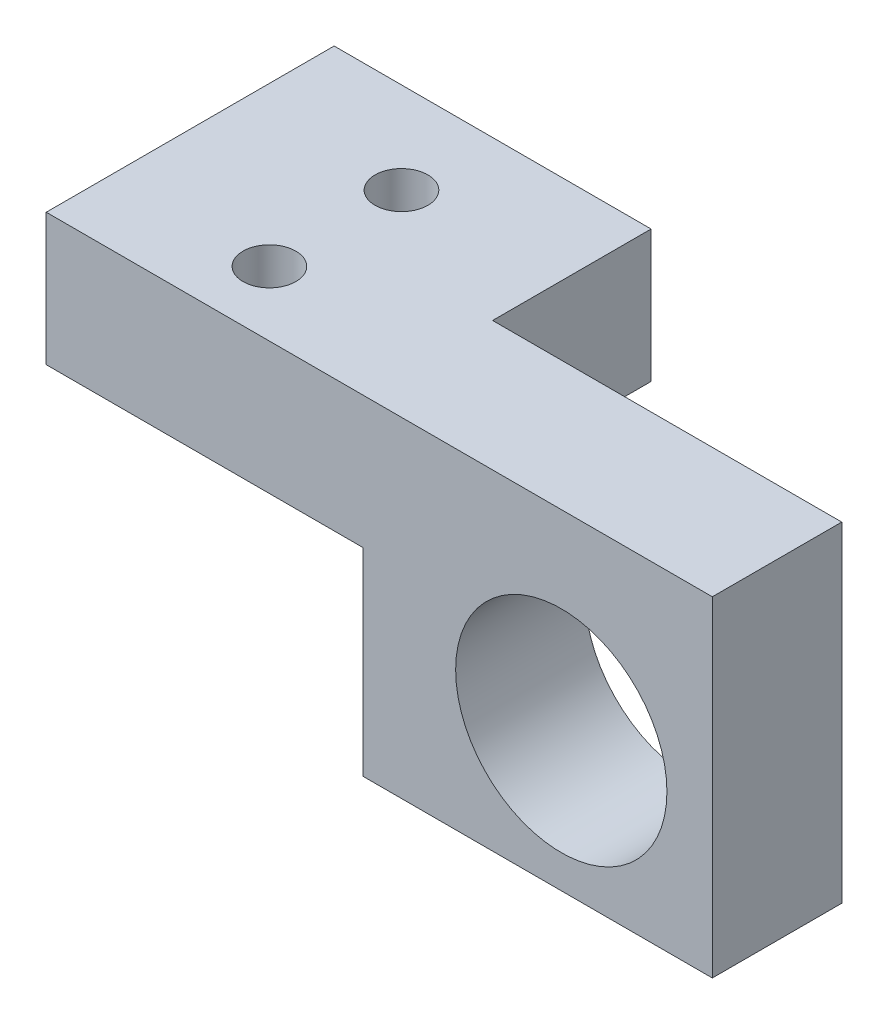
SolidWorks part; units mm, degrees
material "ABS"
ref_plane "Front Plane" through (0, 0, 0) normal (0, 0, 1) x (1, 0, 0)
ref_plane "Top Plane" through (0, 0, 0) normal (0, 1, 0) x (1, 0, 0)
ref_plane "Right Plane" through (0, 0, 0) normal (1, 0, 0) x (0, 0, -1)
sketch "Sketch1" plane through (0, 0, 0) normal (0, 0, 1) x (1, 0, 0)
  line L0 (-24, 15) -> (0, 15)
  line L1 (0, 15) -> (0, 0)
  line L2 (0, 0) -> (93, 0)
  line L3 (93, 0) -> (93, 102.7)
  line L4 (93, 102.7) -> (0, 102.7)
  line L5 (0, 102.7) -> (0, 30)
  line L6 (0, 30) -> (-24, 30)
  line L7 (-24, 30) -> (-24, 15)
  circle A0 centre (15, 10.5) radius 8
  circle A1 centre (70, 72) radius 11
  circle A2 centre (15, 10.5) radius 11
  dimension "D1" = 15
  dimension "D10" = 16
  dimension "D11" = 22
  dimension "D12" = 22
  dimension "D2" = 24
  dimension "D3" = 72.7
  dimension "D4" = 15
  dimension "D5" = 15
  dimension "D6" = 10.5
  dimension "D7" = 82.5061
  dimension "D8" = 72
  dimension "D9" = 93
extrude "Boss-Extrude1" add sketch "Sketch1" along normal blind 4.8 contours A2 L2 L3 L4 L5 L6 L7 L0 L1 A1 | L2 A2 A0 region at (44.5238, 51.0418, 0) region at (8.6656, 19.1141, 0)
sketch "Sketch2" plane through (0, 0, 4.8) normal (0, 0, 1) x (1, 0, 0)
  line L0 (93, 0) -> (93, 102.7) construction
  line L1 (48.1786, 92.7632) -> (93, 92.7632)
  line L2 (48.1786, 92.7632) -> (48.1786, 52.666)
  line L3 (48.1786, 52.666) -> (93, 52.666)
  line L4 (93, 92.7632) -> (93, 52.666)
  line L5 (48.1786, 92.7632) -> (93, 52.666) construction
  line L6 (48.1786, 52.666) -> (93, 92.7632) construction
  circle A0 centre (70, 72) radius 11
  circle A1 centre (70, 72) radius 4.15
  point P8 (70.5893, 72.7146)
  line M4 (93, 0) -> (93, 102.7)
  circle M10 centre (70, 72) radius 11
  dimension "D1" = 22
  dimension "D2" = 8.3
extrude "Boss-Extrude2" add sketch "Sketch2" along normal blind 8.2 contours L2 L3 L1 M4 M10 region at (70.5893, 92.1618, 4.8)
sketch "Sketch3" plane through (0, 0, 4.8) normal (0, 0, 1) x (1, 0, 0)
  line L1 (-24, 15) -> (0, 15)
  line L2 (-24, 15) -> (-24, 30)
  line L3 (-24, 30) -> (0, 30)
  line L4 (0, 15) -> (0, 30)
  line L5 (-24, 15) -> (0, 30) construction
  line L6 (-24, 30) -> (0, 15) construction
  line L7 (0, 0) -> (93, 0)
  line L8 (0, 0) -> (0, 52.666)
  line L9 (0, 52.666) -> (93, 52.666)
  line L10 (93, 0) -> (93, 52.666)
  line L11 (0, 0) -> (93, 52.666) construction
  line L12 (0, 52.666) -> (93, 0) construction
  circle A0 centre (15, 10.5) radius 8
  point P4 (-12, 22.5)
  point P11 (46.5, 26.333)
  circle M1 centre (15, 10.5) radius 8
  line M6 (0, 102.7) -> (0, 30)
  line M7 (0, 30) -> (-24, 30)
  line M8 (-24, 30) -> (-24, 15)
  line M9 (-24, 15) -> (0, 15)
  line M10 (0, 15) -> (0, 0)
  line M11 (0, 0) -> (93, 0)
  line M12 (93, 0) -> (93, 52.666)
  line M13 (93, 52.666) -> (48.1786, 52.666)
extrude "Boss-Extrude3" add sketch "Sketch3" along normal blind 5 contours L4 M9 M7 M8 | L9 L4 M6 M10 M11 M12 M13 M1 region at (-12, 22.5, 4.8) region at (47.8484, 27.0108, 4.8)
sketch "Sketch4" plane through (0, 83.2317, 0) normal (0, -1, 0) x (1, 0, 0)
  line L0 (0, 9.8) -> (0, 4.8) construction
  line L1 (0, 4.8) -> (48.1786, 4.8)
  line L2 (0, 4.8) -> (0, 45.3)
  line L3 (0, 45.3) -> (48.1786, 45.3)
  line L4 (48.1786, 4.8) -> (48.1786, 45.3)
  line L5 (0, 4.8) -> (48.1786, 45.3) construction
  line L6 (0, 45.3) -> (48.1786, 4.8) construction
  line L7 (0, 4.8) -> (48.1786, 4.8) construction
  line L8 (48.1786, 13) -> (48.1786, 9.8) construction
  line L9 (0, 0) -> (93, 0) construction
  line L10 (0, 45.3) -> (-5, 45.3)
  line L11 (0, 45.3) -> (0, 0)
  line L12 (0, 0) -> (-5, 0)
  line L13 (-5, 45.3) -> (-5, 0)
  line L14 (0, 45.3) -> (-5, 0) construction
  line L15 (0, 0) -> (-5, 45.3) construction
  circle A0 centre (13.9465, 30.3) radius 6.35
  circle A1 centre (13.9465, 23.3) radius 18.5
  circle A3 centre (29.4465, 23.3) radius 2
  circle A4 centre (21.6965, 9.8766) radius 2
  circle A5 centre (6.1965, 9.8766) radius 2
  point P10 (24.0893, 25.05)
  point P30 (-2.5, 22.65)
  arc M5 (5.039, 30.9329) -> (22.854, 30.9329) centre (13.9465, 30.3) ccw
  arc M7 (23.1854, 31.0672) -> (4.7077, 31.0672) centre (13.9465, 23.3) cw
  circle M9 centre (21.6965, 9.8766) radius 1.6
  circle M10 centre (6.1965, 9.8766) radius 1.6
  circle M11 centre (-1.5535, 23.3) radius 1.6
  circle M12 centre (6.1965, 36.7234) radius 1.6
  circle M13 centre (21.6965, 36.7234) radius 1.6
  circle M15 centre (27.3699, 31.05) radius 2.1
  circle M16 centre (0.5231, 31.05) radius 2.1
  circle M17 centre (13.9465, 7.8) radius 2.1
  circle M19 centre (13.9465, 23.3) radius 18.5
  dimension "D1" = 12.7
  dimension "D2" = 15
  dimension "D3" = 4
  dimension "D4" = 4
  dimension "D5" = 4
  dimension "D6" = 5
  dimension "D7" = 0
extrude "Boss-Extrude4" add sketch "Sketch4" along normal blind 5 contours L1 L4 L3 M19 | A0 L3 L2 A5 A4 A3 M12 M19 M16 M11 M13 M17 M15 M5 M7 | M5 M7 | M17 | A4 M9 | M9 | M10 | A5 M10 | M15 | L2 M16 | L2 L1 M19 region at (3.3557, 83.2317, 6.6306) region at (34.3643, 83.2317, 27.4815) region at (15.1399, 83.2317, 22.3686) region at (1.1393, 83.2317, 31.05) region at (19.7531, 83.2317, 9.8766) region at (4.2531, 83.2317, 9.8766) region at (21.6965, 83.2317, 9.8766) region at (6.1965, 83.2317, 9.8766) region at (27.3699, 83.2317, 31.05) region at (13.9465, 83.2317, 7.8)
sketch "Sketch5" plane through (48.1786, 0, 0) normal (1, 0, 0) x (0, 0, -1)
  line L0 (-45.3, 83.2317) -> (-13, 92.7632)
  line L1 (-13, 92.7632) -> (-4.8, 92.7632)
  line L2 (-4.8, 92.7632) -> (-4.8, 78.2317)
  line L3 (-4.8, 78.2317) -> (-45.3, 78.2317)
  line L4 (-45.3, 78.2317) -> (-45.3, 83.2317)
extrude "Boss-Extrude5" add sketch "Sketch5" against normal blind 5
sketch "Sketch6" plane through (0, 0, 4.8) normal (0, 0, 1) x (1, 0, 0)
  line L0 (0, 78.2317) -> (0, 52.666) construction
  line L1 (0, 78.2317) -> (48.1786, 78.2317)
  line L2 (0, 78.2317) -> (0, 52.666)
  line L3 (0, 52.666) -> (48.1786, 52.666)
  line L4 (48.1786, 78.2317) -> (48.1786, 52.666)
  line L5 (0, 78.2317) -> (48.1786, 52.666) construction
  line L6 (0, 52.666) -> (48.1786, 78.2317) construction
  line L7 (0, 78.2317) -> (48.1786, 78.2317) construction
  point P4 (24.0893, 65.4489)
extrude "Boss-Extrude6" add sketch "Sketch6" along normal up to surface (5 mm away) up to face at (20.6865, 27.5553, 9.8)
ref_plane "Plane1" through (3.9877, 7.5909, 34.4544) normal (0.9262, 0.2454, -0.2862) x (0.0581, -0.8429, -0.5349)
sketch "Sketch8" plane through (0, 30, 0) normal (0, 1, 0) x (1, 0, 0)
  line L0 (0, 0) -> (-24, -9.8)
  line L1 (-24, -9.8) -> (-24, 0)
  line L2 (-24, 0) -> (0, -9.8)
  circle A0 centre (-12, -4.9) radius 2
  dimension "D1" = 4
extrude "Cut-Extrude1" cut sketch "Sketch8" against normal through all contours A0
sketch "Sketch9" plane through (0, 0, 0) normal (0, 0, -1) x (-1, 0, 0)
  line L1 (0, 30) -> (-93, 30)
  line L2 (0, 30) -> (0, 102.7)
  line L3 (0, 102.7) -> (-93, 102.7)
  line L4 (-93, 30) -> (-93, 102.7)
extrude "Cut-Extrude2" cut sketch "Sketch9" against normal blind 100
sketch "Sketch10" plane through (0, 0, 9.8) normal (0, 0, 1) x (1, 0, 0)
  line L0 (93, 30) -> (-24, 30) construction
  line L1 (93, 0) -> (26.438, 0)
  line L2 (93, 0) -> (93, 30)
  line L3 (93, 30) -> (26.438, 30)
  line L4 (26.438, 0) -> (26.438, 30)
extrude "Cut-Extrude3" cut sketch "Sketch10" against normal blind 100
sketch "Sketch11" plane through (0, 0, 0) normal (0, 0, -1) x (-1, 0, 0)
  line L0 (24, 30) -> (24, 15) construction
  line L1 (0, 15) -> (24, 15)
  line L2 (0, 15) -> (0, 30)
  line L3 (0, 30) -> (24, 30)
  line L4 (24, 15) -> (24, 30)
  line L5 (-26.438, 30) -> (24, 30) construction
extrude "Boss-Extrude7" add sketch "Sketch11" along normal blind 12
sketch "Sketch13" plane through (-24, 0, 0) normal (-1, 0, 0) x (0, 0, 1)
  line L0 (9.8, 30) -> (9.8, 15) construction
  line L1 (-12, 30) -> (9.8, 30)
  line L2 (-12, 30) -> (-12, 25)
  line L3 (-12, 25) -> (9.8, 25)
  line L4 (9.8, 30) -> (9.8, 25)
  dimension "D1" = 5
extrude "Cut-Extrude4" cut sketch "Sketch13" against normal blind 200
sketch "Sketch15" plane through (0, 25, 0) normal (0, 1, 0) x (1, 0, 0)
  circle A0 centre (-12, 5.1) radius 2
  circle A1 centre (-12, -4.9) radius 2 construction
  dimension "D1" = 4
  dimension "D2" = 10
  dimension "D3" = 0
extrude "Cut-Extrude5" cut sketch "Sketch15" against normal blind 200
